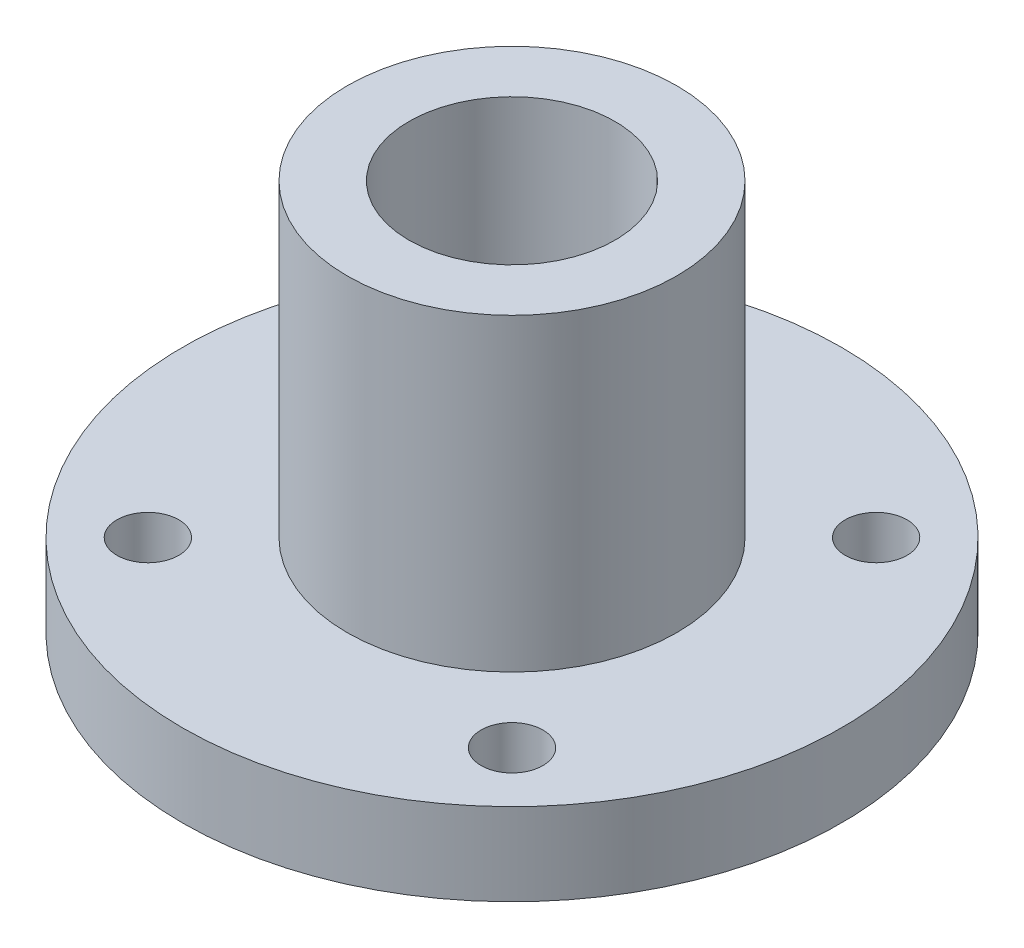
SolidWorks part; units mm, degrees
ref_plane "Front Plane" through (0, 0, 0) normal (0, 0, 1) x (1, 0, 0)
ref_plane "Top Plane" through (0, 0, 0) normal (0, 1, 0) x (1, 0, 0)
ref_plane "Right Plane" through (0, 0, 0) normal (1, 0, 0) x (0, 0, -1)
sketch "Sketch1" plane through (0, 0, 0) normal (0, 1, 0) x (1, 0, 0)
  line L0 (0, 0) -> (0, -16.4946) construction
  line L1 (0, 0) -> (16, 0) construction
  line L2 (0, 0) -> (8.8388, -8.8388) construction
  line L3 (8.8388, -8.8388) -> (11.3137, -11.3137) construction
  circle A0 centre (0, 0) radius 16
  circle A1 centre (8.8388, -8.8388) radius 1.5
  circle A2 centre (0, 0) radius 5
  circle A3 centre (-8.8388, -8.8388) radius 1.5
  circle A4 centre (8.8388, 8.8388) radius 1.5
  circle A5 centre (-8.8388, 8.8388) radius 1.5
  point P8 (6.9463, -7.6307)
  dimension "D1" = 32
  dimension "D2" = 3
  dimension "D3" = 10
  dimension "D4" = 3.5
  dimension "D5" = 45
extrude "Boss-Extrude1" add sketch "Sketch1" along normal blind 4
sketch "Sketch2" plane through (0, 4, 0) normal (0, 1, 0) x (1, 0, 0)
  circle A0 centre (0, 0) radius 8
  circle A1 centre (0, 0) radius 5
  dimension "D1" = 16
extrude "Boss-Extrude2" add sketch "Sketch2" along normal blind 15
